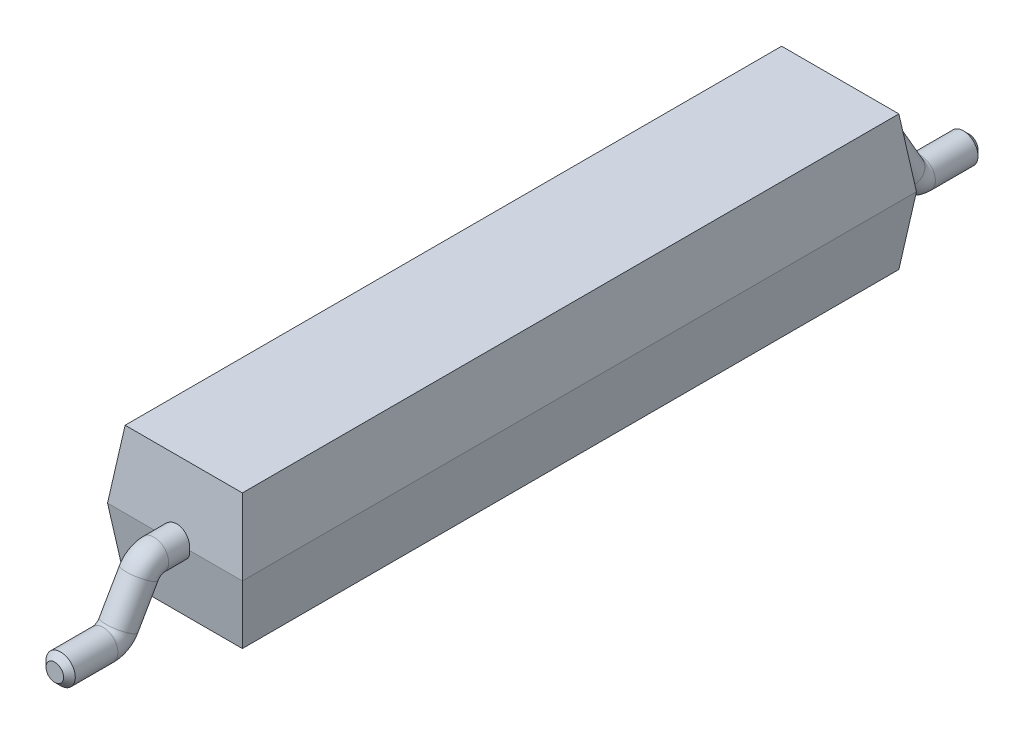
SolidWorks part; units mm, degrees
ref_plane "Front Plane" through (0, 0, 0) normal (0, 0, 1) x (1, 0, 0)
ref_plane "Top Plane" through (0, 0, 0) normal (0, 1, 0) x (1, 0, 0)
ref_plane "Right Plane" through (0, 0, 0) normal (1, 0, 0) x (0, 0, -1)
sketch "Sketch1" plane through (0, 0, 0) normal (0, 0, 1) x (1, 0, 0)
  line L0 (-1, 0) -> (1, 0)
  line L1 (1, 0) -> (1.15, 1.15)
  line L2 (1.15, 1.15) -> (1, 2.3)
  line L3 (1, 2.3) -> (-1, 2.3)
  line L4 (-1, 2.3) -> (-1.15, 1.15)
  line L5 (-1.15, 1.15) -> (-1, 0)
  line L6 (1.15, 1.15) -> (-1.15, 1.15) construction
  dimension "D1" = 2.3
  dimension "D2" = 2.3
  dimension "D3" = 2
extrude "Boss-Extrude1" add sketch "Sketch1" along normal mid plane 11.5
sketch "Sketch2" plane through (0, 0, 0) normal (1, 0, 0) x (0, 0, -1)
  line L0 (5.75, 1.15) -> (5.6, 2.3)
  line L1 (-5.75, 2.3) -> (5.75, 2.3) construction
  line L2 (5.6, 2.3) -> (6.6, 2.3)
  line L3 (6.6, 2.3) -> (6.6, 0)
  line L4 (6.6, 0) -> (5.6, 0)
  line L5 (-5.75, 0) -> (5.75, 0) construction
  line L6 (5.6, 0) -> (5.75, 1.15)
  line L7 (0, 0) -> (0, 2.958) construction
  line L8 (5.75, 1.15) -> (5.75, 2.3) construction
  line L9 (-5.6, 0) -> (-5.75, 1.15)
  line L10 (-6.6, 0) -> (-5.6, 0)
  line L11 (-6.6, 2.3) -> (-6.6, 0)
  line L12 (-5.6, 2.3) -> (-6.6, 2.3)
  line L13 (-5.75, 1.15) -> (-5.6, 2.3)
  dimension "D1" = 0.15
  dimension "D2" = 1
extrude "Cut-Extrude1" cut sketch "Sketch2" along normal through all and the other way blind 11
ref_plane "Plane1" through (0, 0, 5) normal (0, 0, 1) x (1, 0, 0)
sketch "Sketch4" plane through (0, 0, 5) normal (0, 0, 1) x (1, 0, 0)
  line L0 (-1.15, 1.15) -> (1.15, 1.15) construction
  circle A0 centre (0, 1.15) radius 0.25
  dimension "D1" = 0.5
sketch "Sketch5" plane through (0, 0, 0) normal (1, 0, 0) x (0, 0, -1)
  line L0 (-5, 1.15) -> (-6.1072, 1.15)
  line L1 (-5, 1.4) -> (-5, 0.9) construction
  line L2 (-6.367, 1) -> (-6.7134, 0.4)
  line L3 (-6.9732, 0.25) -> (-7.8, 0.25)
  arc A0 (-6.9732, 0.25) -> (-6.7134, 0.4) centre (-6.9732, 0.55) ccw
  arc A1 (-6.367, 1) -> (-6.1072, 1.15) centre (-6.1072, 0.85) cw
  point P9 (-6.8, 0.25)
  dimension "D5" = 0.3
  dimension "D1" = 7.8
  dimension "D2" = 1
  dimension "D3" = 120
  dimension "D4" = 0.25
sweep "Sweep1" add profiles "Sketch4" path "Sketch5"
mirror "Mirror1" about plane through (0, 0, 0) normal (0, 0, 1) of "Sweep1"
chamfer "Chamfer1" distance 0.1 angle 45 2 edges at (0.25, 0.25, -7.8) (0.25, 0.25, 7.8)
